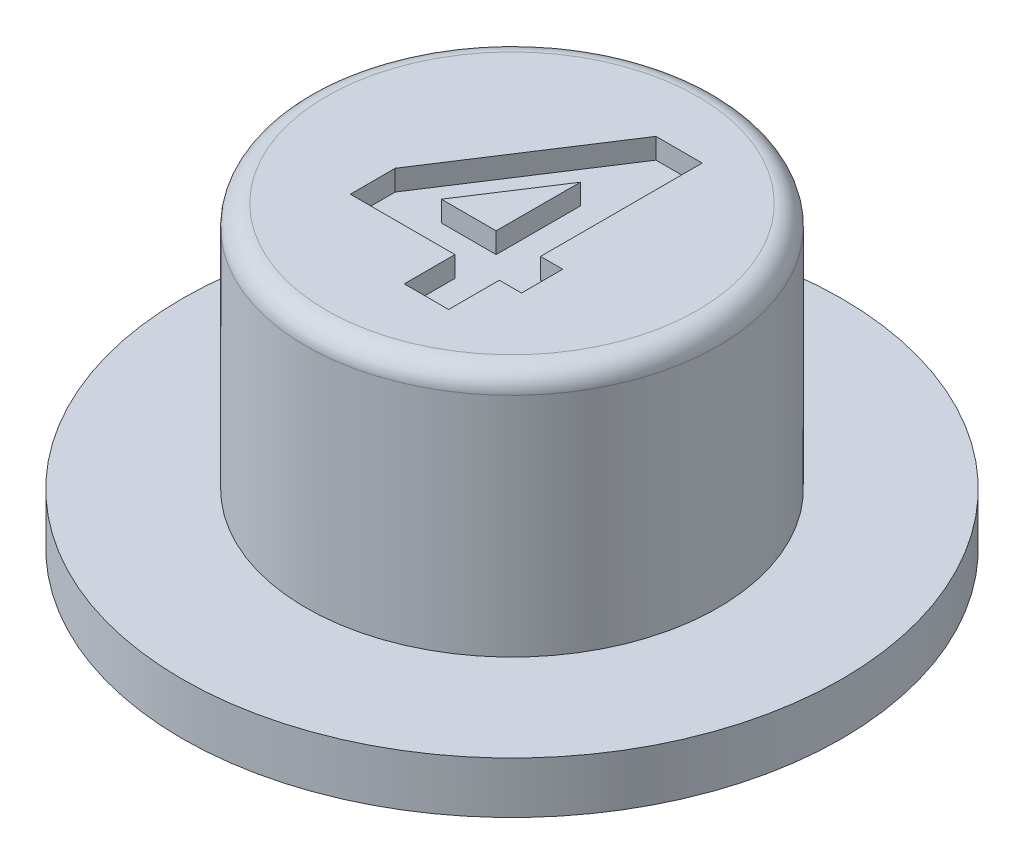
SolidWorks part; units mm, degrees
ref_plane "Front Plane" through (0, 0, 0) normal (0, 0, 1) x (1, 0, 0)
ref_plane "Top Plane" through (0, 0, 0) normal (0, 1, 0) x (1, 0, 0)
ref_plane "Right Plane" through (0, 0, 0) normal (1, 0, 0) x (0, 0, -1)
sketch "Sketch1" plane through (0, 0, 0) normal (0, 0, 1) x (1, 0, 0)
  line L1 (0, 7.25) -> (5, 7.25)
  line L2 (5, 7.25) -> (5, 1.25)
  line L3 (5, 1.25) -> (8, 1.25)
  line L4 (8, 1.25) -> (8, 0)
  line L6 (0, 7.25) -> (0, 6.9292) construction
  line L7 (0, 7.25) -> (0, 0)
  line L10 (0, 0) -> (8, 0)
  dimension "D1" = 5
  dimension "D2" = 3
  dimension "D3" = 6
  dimension "D4" = 1.25
revolve "Revolve1" add sketch "Sketch1" angle 360 about L6
sketch "Sketch2" plane through (0, 0, 0) normal (0, -1, 0) x (1, 0, 0)
  line L1 (-1.75, -1.25) -> (1.75, -1.25)
  line L2 (-1.75, -1.25) -> (-1.75, 1.25)
  line L3 (-1.75, 1.25) -> (1.75, 1.25)
  line L4 (1.75, -1.25) -> (1.75, 1.25)
  line L5 (-1.75, -1.25) -> (1.75, 1.25) construction
  line L6 (-1.75, 1.25) -> (1.75, -1.25) construction
  point P0 (0, 0)
  dimension "D1" = 3.5
  dimension "D2" = 2.5
extrude "Cut-Extrude1" cut sketch "Sketch2" against normal blind 3.5 contours L3 L4 L1 L2
fillet "Fillet1" radius 0.5 1 edges at (-5, 7.25, 0)
sketch "Sketch3" plane through (0, 7.25, 0) normal (0, 1, 0) x (1, 0, 0)
  line L0 (-3.3541, -3) -> (3.3541, -3) construction
  line L1 (0, 0) -> (0, -3) construction
  circle A0 centre (0, 0) radius 4.5 construction
  text T0 "4\r\n" font "Century Gothic" height 6
  dimension "D1" = 3
extrude "Cut-Extrude2" cut sketch "Sketch3" against normal blind 0.5
